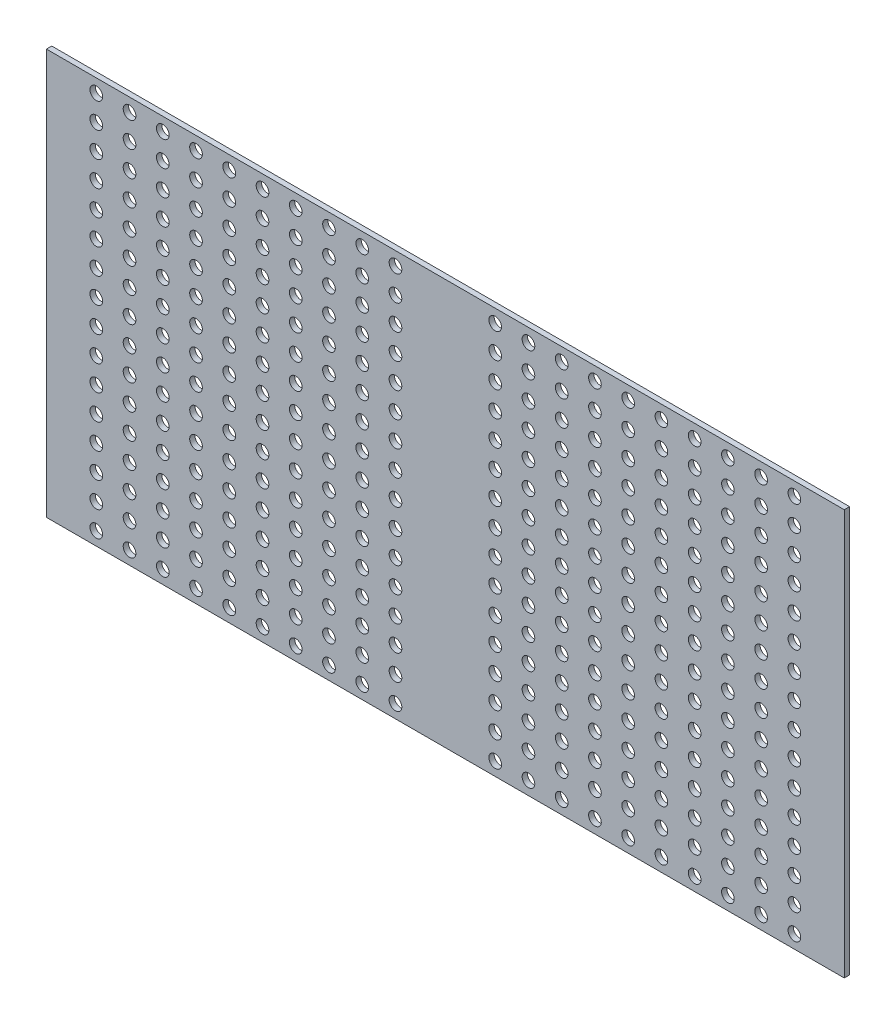
SolidWorks part; units mm, degrees
ref_plane "Front Plane" through (0, 0, 0) normal (0, 0, 1) x (1, 0, 0)
ref_plane "Top Plane" through (0, 0, 0) normal (0, 1, 0) x (1, 0, 0)
ref_plane "Right Plane" through (0, 0, 0) normal (1, 0, 0) x (0, 0, -1)
sketch "Sketch4" plane through (0, 0, 0) normal (0, 0, 1) x (1, 0, 0)
  line L0 (0, 0) -> (0, 50000) construction
  line L1 (0, 0) -> (-50000, 0) construction
  line L3 (600, -305) -> (-600, -305)
  line L4 (600, -305) -> (600, 305)
  line L5 (600, 305) -> (-600, 305)
  line L6 (-600, -305) -> (-600, 305)
  line L7 (600, -305) -> (-600, 305) construction
  line L8 (600, 305) -> (-600, -305) construction
  point P5 (0, 0)
extrude "Boss-Extrude2" add sketch "Sketch4" along normal blind 8 contours L5 L6 L3 L4
sketch "Sketch5" plane through (0, 0, 8) normal (0, 0, 1) x (1, 0, 0)
  line L0 (0, 0) -> (0, 50000) construction
  line L1 (0, 0) -> (50000, 0) construction
  circle A0 centre (-525, 285) radius 9.525
  dimension "D1" = 19.05
  dimension "D2" = 285
  dimension "D3" = 525
extrude "Cut-Extrude1" cut sketch "Sketch5" against normal blind 8
pattern_linear "LPattern1" count 10 spacing 50 along (1, 0, 0) of "Cut-Extrude1"
pattern_linear "LPattern2" count 16 spacing 38 along (0, -1, 0) of "LPattern1", "Cut-Extrude1"
mirror "Mirror1" about plane through (0, 0, 0) normal (1, 0, 0) of "LPattern2", "LPattern1"
